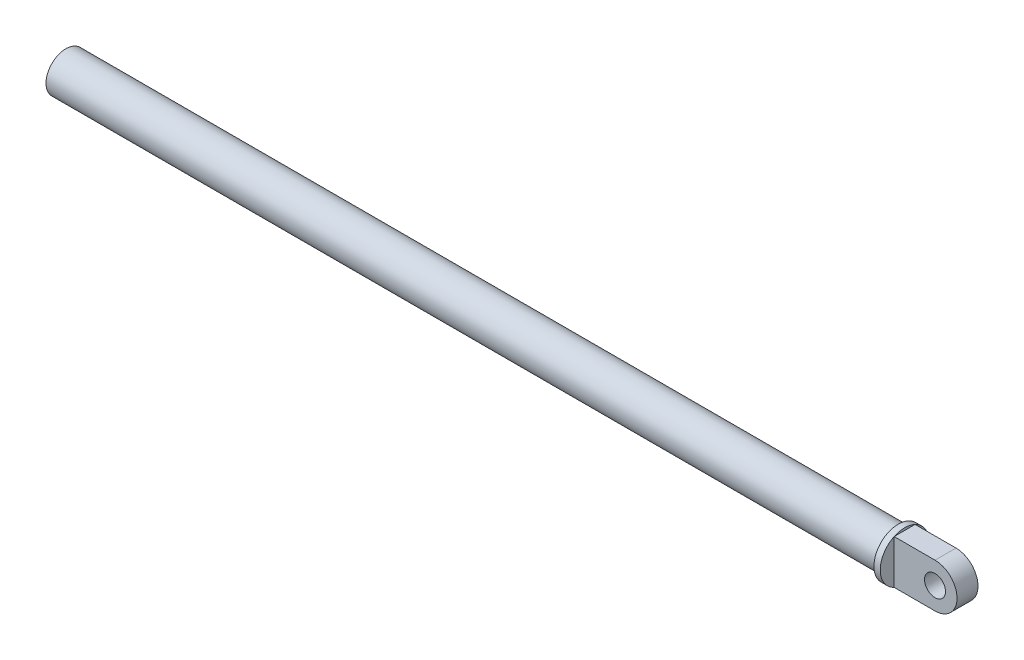
SolidWorks part; units mm, degrees
ref_plane "Front Plane" through (0, 0, 0) normal (0, 0, 1) x (1, 0, 0)
ref_plane "Top Plane" through (0, 0, 0) normal (0, 1, 0) x (1, 0, 0)
ref_plane "Right Plane" through (0, 0, 0) normal (1, 0, 0) x (0, 0, -1)
sketch "Sketch1" plane through (0, 0, 0) normal (0, 0, 1) x (1, 0, 0)
  line L1 (-50.8638, 14.1528) -> (-20.8638, 14.1528)
  line L2 (-50.8638, 14.1528) -> (-50.8638, -6.8472)
  line L3 (-50.8638, -6.8472) -> (-20.8638, -6.8472)
  line L4 (-20.8638, 14.1528) -> (-20.8638, -6.8472)
  circle A0 centre (-31.3638, 3.6528) radius 10.5
  circle A1 centre (-31.3638, 3.6528) radius 5
  dimension "D3" = 10.5
  dimension "D1" = 30
  dimension "D2" = 21
  dimension "D4" = 10.5
extrude "Boss-Extrude1" add sketch "Sketch1" along normal blind 10 contours A0 A1 | A0 L1 L2 L3 region at (-44.9931, 3.6528, 0) region at (-24.1492, 10.8674, 0)
sketch "Sketch2" plane through (-50.8638, 0, 0) normal (-1, 0, 0) x (0, 0, 1)
  line L0 (0, 14.1528) -> (10, 14.1528)
  line L1 (10, 14.1528) -> (5, 14.1528)
  line L2 (5, 14.1528) -> (5, -6.8472)
  line L3 (10, -6.8472) -> (0, -6.8472) construction
  circle A0 centre (5, 3.6528) radius 11.6297
  circle A1 centre (5, 3.6528) radius 9.5
  circle A2 centre (5, 3.6528) radius 8
  line M1 (0, 14.1528) -> (0, -6.8472)
  line M2 (0, -6.8472) -> (10, -6.8472)
  line M3 (10, -6.8472) -> (10, 14.1528)
  line M4 (10, 14.1528) -> (0, 14.1528)
  dimension "D1" = 19
  dimension "D2" = 16
extrude "Boss-Extrude9" add sketch "Sketch2" along normal blind 3 contours A1 L2 L0 M1 | A1 L2 M3 M4 | A2 M1 | A2 M3 | A1 A0 M1 | A0 L0 M4 | A1 A0 M3 | A0 M2 | A1 L2 M1 M2 | A1 L2 M2 M3 | A2 A1 L2 M1 | A2 L2 A1 M3 | A2 L2 A1 M1 | A2 A1 L2 M3 | A2 A1 M3 | A2 A1 M1 | A2 L2 M3 | L2 A2 M1 region at (-50.8638, 14.6066, 5) region at (-50.8638, 12.9417, -0.2202) region at (-50.8638, 13.3632, 2.1007) region at (-50.8638, 13.3632, 7.8993) region at (-50.8638, 9.7442, 14.6474) region at (-50.8638, -7.301, 5) region at (-50.8638, -6.0576, 2.1007) region at (-50.8638, 10.8142, -0.1677) region at (-50.8638, 11.8675, 2.419) region at (-50.8638, 11.8675, 7.581) region at (-50.8638, 8.1945, 13.1526) region at (-50.8638, -6.0576, 7.8993) region at (-50.8638, -4.5619, 2.419) region at (-50.8638, 3.6528, -1.2217) region at (-50.8638, 3.6528, 2.5957) region at (-50.8638, 3.6528, 7.4043) region at (-50.8638, 3.6528, 11.2217) region at (-50.8638, -4.5619, 7.581)
extrude "Boss-Extrude10" add sketch "Sketch2<8>" along normal blind 400 contours A2 L2 A1 M1 | A2 A1 L2 M3 | A2 A1 M3 | A2 A1 M1 | A2 A1 L2 M1 | A2 L2 A1 M3 region at (-50.8638, 10.8142, -0.1677) region at (-50.8638, 11.8675, 2.419) region at (-50.8638, 11.8675, 7.581) region at (-50.8638, 8.1945, 13.1526) region at (-50.8638, -4.5619, 2.419) region at (-50.8638, -4.5619, 7.581)
sketch "Sketch2<8>" plane through (-50.8638, 0, 0) normal (-1, 0, 0) x (0, 0, 1) same geometry as "Sketch2"
